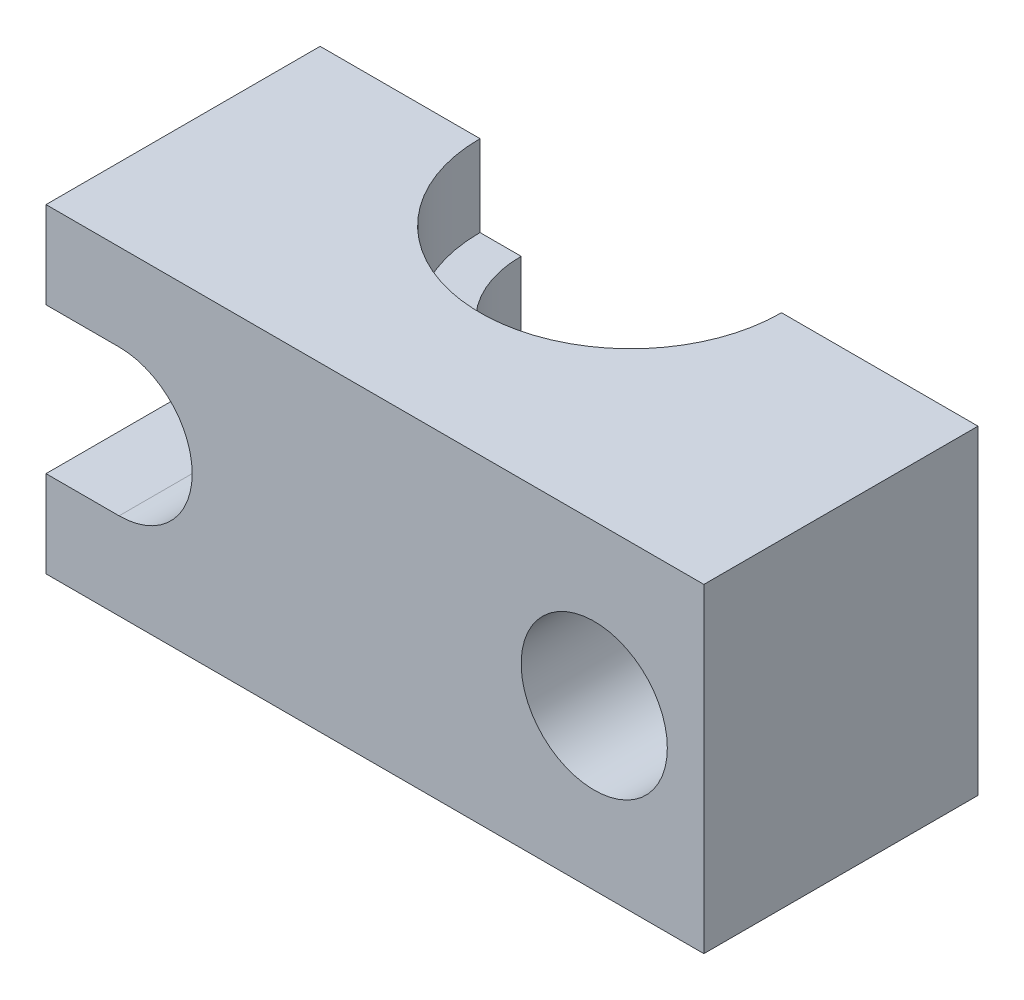
SolidWorks part; units mm, degrees
ref_plane "Front Plane" through (0, 0, 0) normal (0, 0, 1) x (1, 0, 0)
ref_plane "Top Plane" through (0, 0, 0) normal (0, 1, 0) x (1, 0, 0)
ref_plane "Right Plane" through (0, 0, 0) normal (1, 0, 0) x (0, 0, -1)
sketch "Sketch1" plane through (0, 0, 0) normal (0, 0, 1) x (1, 0, 0)
  line L1 (20.8485, 34.043) -> (56.8485, 34.043)
  line L2 (20.8485, 34.043) -> (20.8485, 16.543)
  line L3 (20.8485, 16.543) -> (56.8485, 16.543)
  line L4 (56.8485, 34.043) -> (56.8485, 16.543)
  dimension "D1" = 17.5
  dimension "D2" = 36
extrude "Boss-Extrude1" add sketch "Sketch1" along normal blind 15
sketch "Sketch2" plane through (0, 0, 15) normal (0, 0, 1) x (1, 0, 0)
  line L0 (56.8485, 25.293) -> (20.8485, 25.293) construction
  line L1 (56.8485, 16.543) -> (56.8485, 34.043) construction
  line L2 (20.8485, 34.043) -> (20.8485, 16.543) construction
  circle A0 centre (50.8485, 25.293) radius 1.75
  circle A1 centre (24.8485, 25.293) radius 1.75
  dimension "D1" = 3.5
  dimension "D2" = 6
  dimension "D3" = 26
extrude "Cut-Extrude1" cut sketch "Sketch2" against normal up to surface (15 mm away) up to face at (38.8485, 25.293, 0)
sketch "Sketch3" plane through (0, 0, 15) normal (0, 0, 1) x (1, 0, 0)
  line L0 (24.8485, 29.293) -> (20.8485, 29.293)
  line L1 (20.8485, 34.043) -> (20.8485, 16.543) construction
  line L2 (20.8485, 29.293) -> (20.8485, 21.293)
  line L3 (20.8485, 21.293) -> (24.8485, 21.293)
  circle A0 centre (50.8485, 25.293) radius 4
  arc A1 (24.8485, 21.293) -> (24.8485, 29.293) centre (24.8485, 25.293) ccw
  dimension "D1" = 8
extrude "Cut-Extrude2" cut sketch "Sketch3" against normal offset from surface (11 mm away) 4 up to face at (26.5985, 25.293, 0)
ref_axis "Axis1" through (24.8485, 25.293, 0) along (0, 0, 1)
ref_axis "Axis2" through (50.8485, 25.293, 0) along (0, 0, 1)
ref_plane "Plane1" through (50.8485, 0, 0) normal (-1, 0, 0) x (0, 0, 1)
ref_plane "Plane2" through (24.8485, 0, 0) normal (-1, 0, 0) x (0, 0, 1)
ref_plane "Plane3" through (37.8485, 0, 0) normal (-1, 0, 0) x (0, 0, 1)
sketch "Sketch4" plane through (37.8485, 0, 0) normal (-1, 0, 0) x (0, 0, 1)
  line L0 (0, 16.543) -> (0, 34.293)
  line L2 (0, 34.293) -> (8.25, 34.293)
  line L3 (8.25, 34.293) -> (8.25, 29.593)
  line L4 (8.25, 29.593) -> (6, 29.593)
  line L5 (6, 29.593) -> (6, 24.993)
  line L6 (6, 24.993) -> (8.25, 24.993)
  line L7 (8.25, 24.993) -> (8.25, 21.993)
  line L8 (8.25, 21.993) -> (6, 21.993)
  line L9 (6, 21.993) -> (6, 16.543)
  line L10 (15, 16.543) -> (0, 16.543) construction
  line L11 (6, 16.543) -> (0, 16.543)
  line L12 (15, 34.043) -> (0, 34.043) construction
  dimension "D1" = 8.25
  dimension "D2" = 6
  dimension "D3" = 4.7
  dimension "D4" = 3
  dimension "D5" = 4.6
  dimension "D6" = 0.25
revolve "Cut-Revolve1" cut sketch "Sketch4" angle 360 about L0
